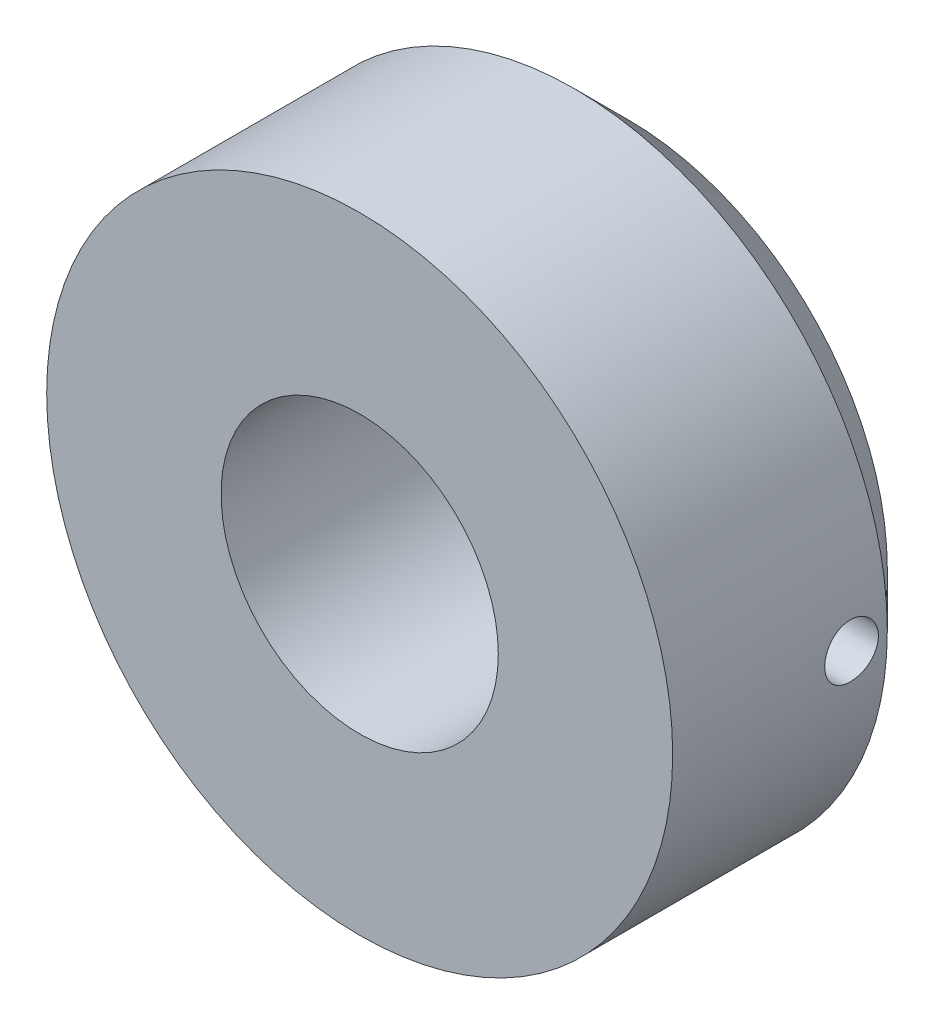
SolidWorks part; units mm, degrees
ref_plane "Front Plane" through (0, 0, 0) normal (0, 0, 1) x (1, 0, 0)
ref_plane "Top Plane" through (0, 0, 0) normal (0, 1, 0) x (1, 0, 0)
ref_plane "Right Plane" through (0, 0, 0) normal (1, 0, 0) x (0, 0, -1)
ref_axis "Z" through (0, 0, 543.0939) along (0, 0, -1)
ref_axis "X" through (17.0818, 0, 0) along (-1, 0, 0)
ref_axis "Y" through (0, 19.25, 0) along (0, -1, 0)
sketch "Sketch1" plane through (0, 0, 0) normal (0, 0, 1) x (1, 0, 0)
  circle A0 centre (0, 0) radius 17.5
  circle A1 centre (0, 0) radius 8.75
  dimension "D1" = 35
  dimension "D2" = 17.5
extrude "Boss-Extrude1" add sketch "Sketch1" against normal blind 5 and the other way blind 10
sketch "Sketch2" plane through (0, 0, 0) normal (0, 1, 0) x (1, 0, 0)
  line L0 (-19.25, 0) -> (19.25, 0) construction
  line L1 (0, -8.25) -> (0, 8.25) construction
  circle A0 centre (0, 0) radius 1.5
  dimension "D1" = 3
extrude "Cut-Extrude1" cut sketch "Sketch2" against normal through all
sketch "Sketch3" plane through (0, 0, 0) normal (1, 0, 0) x (0, 0, -1)
  circle A0 centre (0, 0) radius 1.5
  dimension "D1" = 3
extrude "Cut-Extrude2" cut sketch "Sketch3" along normal through all
chamfer "Chamfer1" distance 3 angle 45 1 edges at (17.5, 0, -5)
sketch "Sketch4" plane through (0, 0, 0) normal (0, 0, 1) x (1, 0, 0)
  circle A0 centre (0, 0) radius 8.75
  circle A2 centre (0, 0) radius 8.75 construction
  circle A3 centre (0, 0) radius 7.75
  dimension "D1" = 1
extrude "Boss-Extrude2" add sketch "Sketch4" along normal up to surface and the other way up to surface up to face at (17.5, 0, 10) other way up to face at (14.5, 0, -5)
equation "\"EyeDiameter\" = 35"
equation "\"BasePlaneDistance\" = \"EyeDiameter\"/2+19.84"
equation "\"EyeClearance\" = 2"
equation "\"EyeOD\"= \"EyeDiameter\""
equation "\"D1@Sketch1\"=\"EyeOD\""
equation "\"D2@Sketch1\"=\"EyeDiameter\"*0.5"
equation "\"pinHoleDiameter\"= 3"
equation "\"D1@Sketch2\"=\"pinHoleDiameter\""
equation "\"D1@Sketch3\"=\"pinHoleDiameter\""
